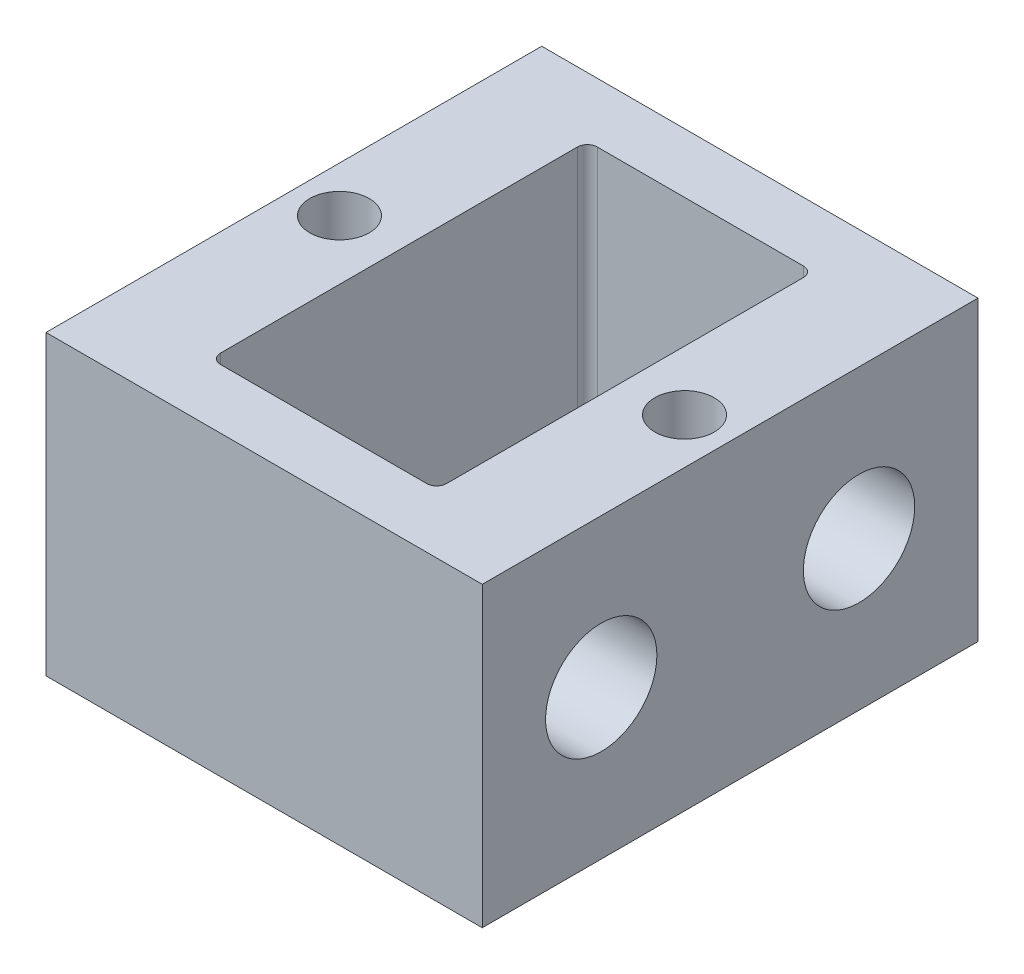
SolidWorks part; units mm, degrees
ref_plane "Front Plane" through (0, 0, 0) normal (0, 0, 1) x (1, 0, 0)
ref_plane "Top Plane" through (0, 0, 0) normal (0, 1, 0) x (1, 0, 0)
ref_plane "Right Plane" through (0, 0, 0) normal (1, 0, 0) x (0, 0, -1)
sketch "Sketch1" plane through (0, 0, 0) normal (0, 1, 0) x (1, 0, 0)
  line L1 (-11, 12.5) -> (11, 12.5)
  line L2 (-11, 12.5) -> (-11, -12.5)
  line L3 (-11, -12.5) -> (11, -12.5)
  line L4 (11, 12.5) -> (11, -12.5)
  line L5 (-11, 12.5) -> (11, -12.5) construction
  line L6 (-11, -12.5) -> (11, 12.5) construction
  point P0 (0, 0)
  dimension "D1" = 22
  dimension "D2" = 25
extrude "Boss-Extrude1" add sketch "Sketch1" along normal blind 15
sketch "Sketch2" plane through (0, 15, 0) normal (0, 1, 0) x (1, 0, 0)
  line L0 (8.7, -10.2) -> (8.7, -1.5) construction
  line L2 (-8.7, 10.2) -> (-8.7, 1.5) construction
  line L4 (11, -12.5) -> (11, 12.5)
  line L5 (11, 12.5) -> (-11, 12.5)
  line L6 (-11, 12.5) -> (-11, -12.5)
  line L7 (-11, -12.5) -> (11, -12.5)
  line L8 (11, -12.5) -> (11, 12.5) construction
  line L9 (11, 12.5) -> (-11, 12.5) construction
  line L10 (-11, 12.5) -> (-11, -12.5) construction
  line L11 (-11, -12.5) -> (11, -12.5) construction
  line L12 (-8.7, -1.5) -> (-8.7, -10.2) construction
  line L13 (-8.7, 10.2) -> (-8.7, -10.2) construction
  line L14 (8.7, 1.5) -> (8.7, 10.2) construction
  line L15 (8.7, -10.2) -> (8.7, 10.2) construction
  line L21 (5.7, -9.5) -> (5.7, 9.5)
  line L22 (-5.7, 9.5) -> (5.7, 9.5)
  line L23 (8.7, 10.2) -> (-8.7, 10.2) construction
  line L24 (-5.7, -9.5) -> (5.7, -9.5)
  line L25 (-8.7, -10.2) -> (8.7, -10.2) construction
  line L26 (-11, -12.5) -> (11, -12.5) construction
  line L27 (-5.7, 9.5) -> (-5.7, -9.5)
  arc A0 (-8.7, -1.5) -> (-8.7, 1.5) centre (-8.7, 0) ccw construction
  arc A1 (8.7, 1.5) -> (8.7, -1.5) centre (8.7, 0) ccw construction
  point P11 (-7.2, 0)
  point P15 (-11, 0)
  point P18 (7.2, 0)
  dimension "D3" = 3
  dimension "D4" = 17.4
  dimension "D2" = 17.4
  dimension "D5" = 1.5
  dimension "D6" = 1.5
  dimension "D7" = 3
  dimension "D8" = 3
  dimension "D1" = 0
hole_wizard "M3 Clearance Hole1" positions "Sketch3" profile "Sketch4" hole size "M3" standard "ANSI Metric" end condition through all
sketch "Sketch3" plane through (0, 15, 0) normal (0, 1, 0) x (1, 0, 0)
  point P0 (-8.7, 0)
  point P3 (8.7, 0)
sketch "Sketch4" plane through (-8.7, 15, 0) normal (1, 0, 0) x (0, 0, 1)
  line L0 (0, 0) -> (0, 15)
  line L1 (0, 15) -> (1.5, 15)
  line L2 (1.5, 15) -> (1.5, 0)
  line L5 (1.5, 0) -> (0, 0)
  line L11 (0, -6.35) -> (0, 107.95) construction
  dimension "Thru Hole Dia." = 3
  dimension "Thru Hole Depth" = 15
extrude "Cut-Extrude1" cut sketch "Sketch2" against normal through all
hole_wizard "for m4 heat set" positions "Sketch6" profile "Sketch7" hole size "#2" standard "ANSI Inch" end condition up to next
sketch "Sketch6" plane through (11, 0, 0) normal (1, 0, 0) x (0, 0, -1)
  line L0 (-12.5, 0) -> (12.5, 0) construction
  line L3 (-12.5, 15) -> (12.5, 15) construction
  line L4 (6.5, 7.5) -> (-6.5, 7.5) construction
  point P0 (-6.5, 7.5)
  point P3 (6.5, 7.5)
  point P16 (0, 15)
  point P25 (0, 7.5)
  dimension "D2" = 13
  dimension "D3" = 7.5
sketch "Sketch7" plane through (11, 7.5, 6.5) normal (0, 1, 0) x (0, 0, -1)
  line L0 (0, 0) -> (0, 5.3)
  line L1 (0, 5.3) -> (2.8067, 5.3)
  line L2 (2.8067, 5.3) -> (2.8067, 0)
  line L5 (2.8067, 0) -> (0, 0)
  line L11 (0, -6.35) -> (0, 107.95) construction
  dimension "Thru Hole Dia." = 5.6134
  dimension "Thru Hole Depth" = 5.3
sketch "Sketch5" plane through (11, 0, 0) normal (1, 0, 0) x (0, 0, -1)
  line L0 (-5, 7.5) -> (5, 7.5) construction
  line L1 (-12.5, 15) -> (12.5, 15) construction
  line L2 (12.5, 15) -> (12.5, 0) construction
  point P0 (-5, 7.5)
  point P1 (5, 7.5)
  point P6 (0, 15)
  point P7 (0, 7.5)
  point P11 (12.5, 7.5)
  dimension "D1" = 10
fillet "Fillet1" radius 0.5 4 edges at (5.7, 7.5, -9.5) (-5.7, 7.5, 9.5) (-5.7, 7.5, -9.5) (5.7, 7.5, 9.5)
